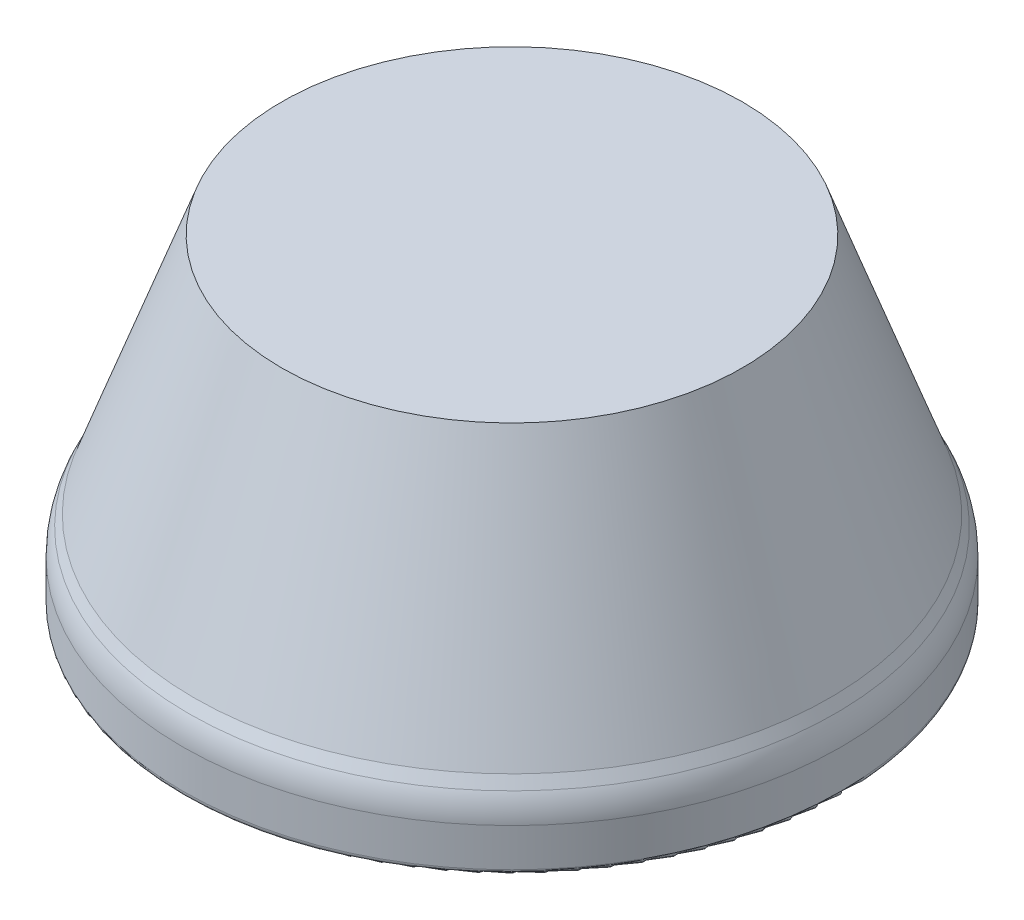
SolidWorks part; units mm, degrees
note: '?' marks a value the reader was unsure of. The reader was unsure of these and kept them because the rebuilt part matched: shared geometry of "Sketch33<11>", "Sketch33<12>", "Sketch33<14>".
ref_plane "Front Plane" through (0, 0, 0) normal (0, 0, 1) x (1, 0, 0)
ref_plane "Top Plane" through (0, 0, 0) normal (0, 1, 0) x (1, 0, 0)
ref_plane "Right Plane" through (0, 0, 0) normal (1, 0, 0) x (0, 0, -1)
sketch "Sketch33" plane through (0, 0, 0) normal (0, 1, 0) x (1, 0, 0)
  circle A0 centre (0, 0) radius 27.6
  circle A1 centre (0, 0) radius 28.6
  circle A2 centre (0, 0) radius 26
  circle A3 centre (0, 0) radius 20
extrude "Boss-Extrude7" add sketch "Sketch33" against normal blind 5 separate body contours A1 A0
extrude "Boss-Extrude8" add sketch "Sketch33<11>" along normal blind 1 from offset 22 separate body contours A3
sketch "Sketch33<11>" plane through (0, 0, 0) normal (0, 1, 0) x (1, 0, 0) same geometry as "Sketch33"
extrude "Boss-Extrude9" add sketch "Sketch33<12>" along normal blind 2 separate body contours A0 A2
sketch "Sketch33<12>" plane through (0, 0, 0) normal (0, 1, 0) x (1, 0, 0) same geometry as "Sketch33"
loft "Loft5" add section edge at (0, 0, 28.6) section edge at (0, 2, 27.6)
extrude "Cut-Extrude1" cut sketch "Sketch33<14>" along normal blind 4.5 contours A2 A3 | A3
sketch "Sketch33<14>" plane through (0, 0, 0) normal (0, 1, 0) x (1, 0, 0) same geometry as "Sketch33"
loft "Loft6" add section edge at (0, 2, 27.6) section edge at (0, 23, 20)
sketch "Sketch35" plane through (0, 0, 0) normal (0, 0, 1) x (1, 0, 0)
  line L0 (-26, 2) -> (-19, 22)
  line L1 (-19, 22) -> (0, 22)
  line L2 (-26, 2) -> (0, 2)
  line L4 (-27.6, 2) -> (27.6, 2) construction
  line L5 (0, 22) -> (0, 2)
ref_axis "Axis1" through (0, 0, 0) along (0, 1, 0)?
revolve "Cut-Revolve4" cut sketch "Sketch35" angle 360 about L5
fillet "Fillet1" radius 0.5 2 edges at (0, -5, 28.6) (0, -5, 27.6)
fillet "Fillet3" radius 5 1 edges at (0, 0, 28.6)
